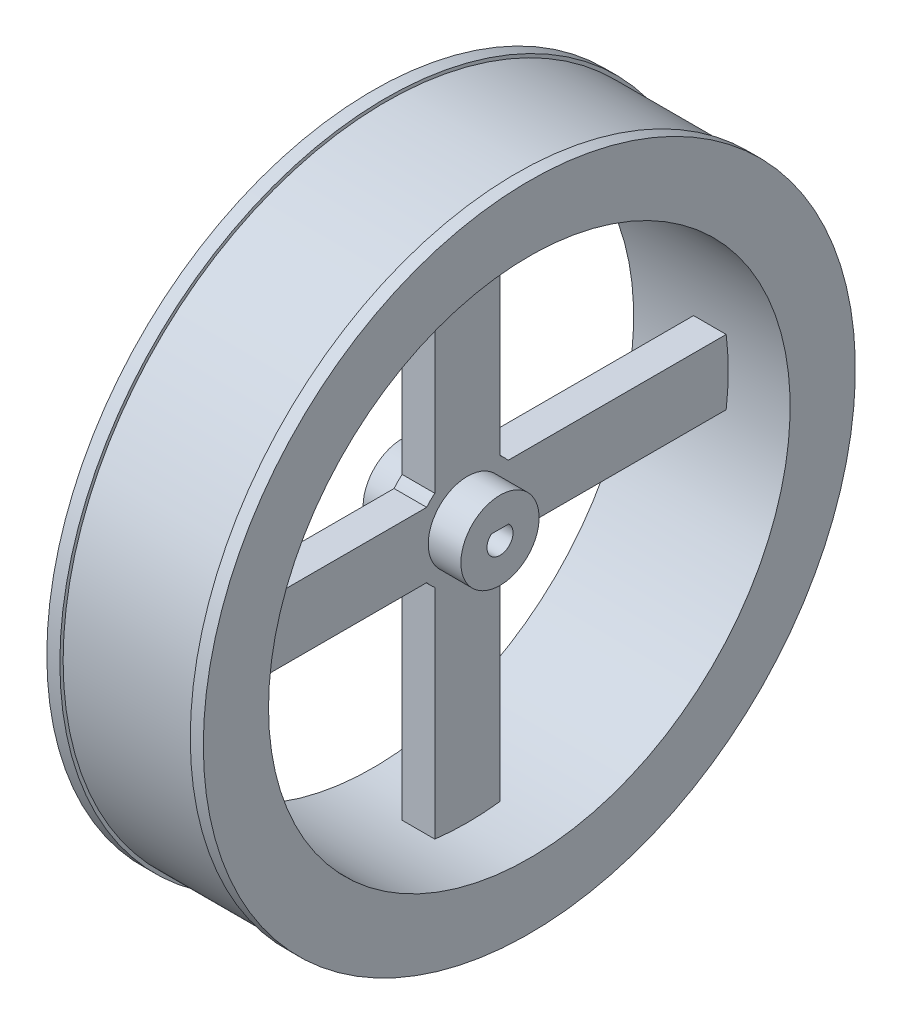
SolidWorks part; units mm, degrees
ref_plane "Front Plane" through (0, 0, 0) normal (0, 0, 1) x (1, 0, 0)
ref_plane "Top Plane" through (0, 0, 0) normal (0, 1, 0) x (1, 0, 0)
ref_plane "Right Plane" through (0, 0, 0) normal (1, 0, 0) x (0, 0, -1)
sketch "Sketch1" plane through (0, 0, 0) normal (0, 0, 1) x (1, 0, 0)
  line L0 (0, 0) -> (41532.2986, 0) construction
  line L1 (-12, 50) -> (-12, 40)
  line L3 (12, 40) -> (12, 50)
  line L4 (12, 50) -> (10, 50)
  line L5 (10, 50) -> (10, 49.5)
  line L6 (10, 49.5) -> (-10, 49.5)
  line L7 (-10, 49.5) -> (-10, 50)
  line L8 (-10, 50) -> (-12, 50)
  line L9 (-12, 40) -> (12, 40)
  line L10 (7.5, 6) -> (-7.5, 6)
  line L11 (-7.5, 6) -> (-7.5, 0)
  line L12 (-7.5, 0) -> (7.5, 0)
  line L13 (7.5, 0) -> (7.5, 6)
  point P9 (0, 0)
  point P14 (0, 6)
  point P15 (0, 40)
  dimension "D1" = 100
  dimension "D2" = 0.5
  dimension "D3" = 2
  dimension "D4" = 20
  dimension "D5" = 10
  dimension "D6" = 12
  dimension "D7" = 15
revolve "Revolve1" add sketch "Sketch1" angle 360 about L0
sketch "Sketch2" plane through (0, 0, 0) normal (1, 0, 0) x (0, 0, -1)
  line L2 (0, 0) -> (0, 50000) construction
  line L9 (-5, 6.245) -> (-5, 39.6863)
  line L10 (5, 6.245) -> (5, 39.6863)
  arc A0 (-5, 39.6863) -> (5, 39.6863) centre (0, 0) cw
  arc A11 (-5, 6.245) -> (5, 6.245) centre (0, 0) ccw
  circle A12 centre (0, 0) radius 40 construction
  circle A13 centre (0, 0) radius 6
  circle A14 centre (0, 0) radius 6
  dimension "D1" = 16
  dimension "D2" = 10
  dimension "D3" = 0
extrude "Boss-Extrude1" add sketch "Sketch2" along normal mid plane 5
sketch "Sketch3" plane through (7.5, 0, 0) normal (1, 0, 0) x (0, 0, -1)
  line L0 (-1.3229, 1.5) -> (1.3229, 1.5)
  arc A0 (-1.3229, 1.5) -> (1.3229, 1.5) centre (0, 0) ccw
  point P1 (0, 0)
  dimension "D1" = 4
  dimension "D2" = 1.5
extrude "Cut-Extrude1" cut sketch "Sketch3" against normal through all both and the other way through all
pattern_circular "CirPattern1" count 4 over 360 about axis through (-12, 0, 0) along (1, 0, 0) of "Boss-Extrude1" reverse direction yes
